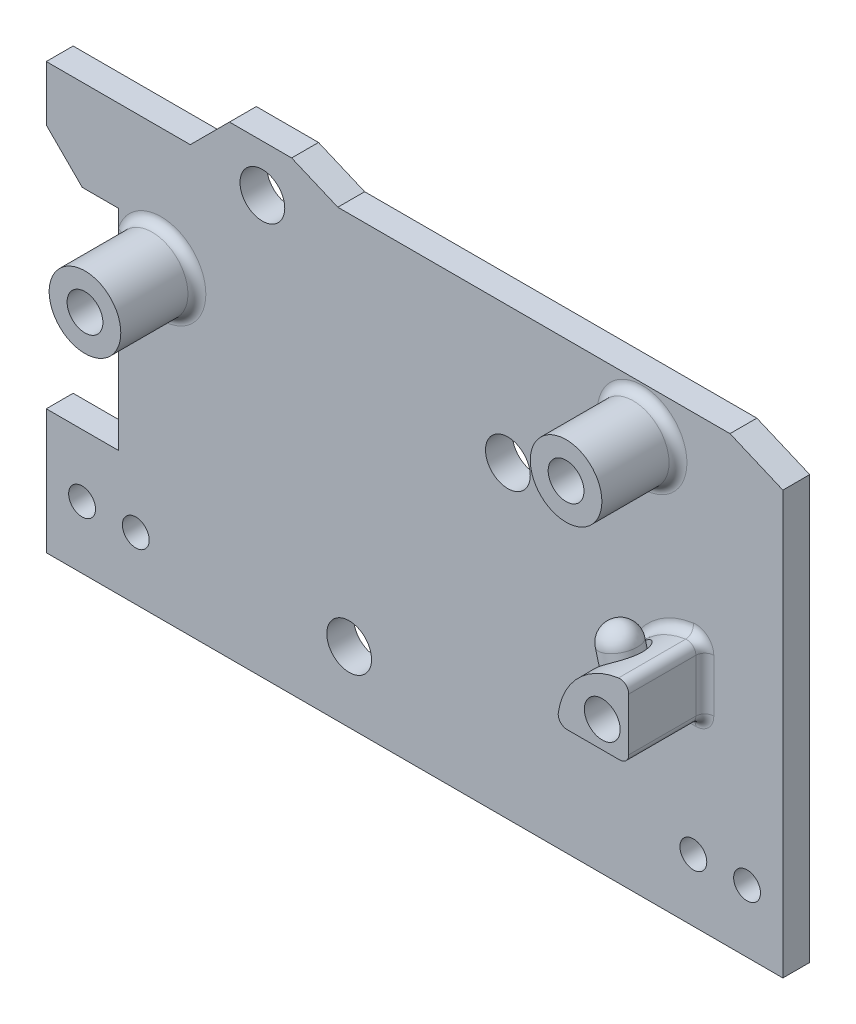
SolidWorks part; units mm, degrees
ref_plane "정면" through (0, 0, 0) normal (0, 0, 1) x (1, 0, 0)
ref_plane "윗면" through (0, 0, 0) normal (0, 1, 0) x (1, 0, 0)
ref_plane "우측면" through (0, 0, 0) normal (1, 0, 0) x (0, 0, -1)
sketch "스케치2" plane through (0, 0, 0) normal (0, 0, 1) x (1, 0, 0)
  line L0 (-41.1383, 21.5701) -> (-25.0531, 21.5701)
  line L1 (-25.0531, 21.5701) -> (-20.6777, 25.9456)
  line L2 (-20.6777, 25.9456) -> (-13.7287, 25.9456)
  line L3 (-13.7287, 25.9456) -> (-8.5741, 23.7579)
  line L4 (-8.5741, 23.7579) -> (35.2319, 23.7579)
  line L5 (35.2319, 23.7579) -> (41.1383, 21.2511)
  line L6 (41.1383, 21.2511) -> (41.1383, -25.9456)
  line L7 (41.1383, -25.9456) -> (-41.1383, -25.9456)
  line L8 (-41.1383, -25.9456) -> (-41.1383, -12.0209)
  line L9 (-41.1383, -12.0209) -> (-33.0957, -12.0209)
  line L10 (-33.0957, -12.0209) -> (-33.0957, 11.4038)
  line L11 (-33.0957, 11.4038) -> (-37.117, 11.4038)
  line L12 (-37.117, 11.4038) -> (-41.1383, 15.4251)
  line L13 (-41.1383, 15.4251) -> (-41.1383, 21.5701)
  line L14 (25.5434, -5.467) -> (31.4219, -5.467)
  line L15 (32.4219, -4.467) -> (32.4219, 1.4115)
  line L16 (32.1291, -5.1741) -> (26.7998, 0.1551) construction
  line L17 (0, 0) -> (-17, 0) construction
  line L18 (-17, 0) -> (-17, 20.7) construction
  circle A0 centre (-17, 20.7) radius 2.5
  circle A1 centre (-28.3144, 7.9767) radius 4
  circle A2 centre (25.4219, 18.533) radius 4
  circle A3 centre (-7.3061, -18.1076) radius 2.5
  circle A4 centre (10.4219, 8.533) radius 2.5
  circle A5 centre (-28.3144, 7.9767) radius 2
  circle A6 centre (25.4219, 18.533) radius 2
  arc A7 (31.2781, 2.4011) -> (24.5538, -4.3232) centre (32.4219, -5.467) ccw
  arc A8 (31.4219, -5.467) -> (32.4219, -4.467) centre (31.4219, -4.467) ccw
  arc A9 (32.4219, 1.4115) -> (31.2781, 2.4011) centre (31.4219, 1.4115) ccw
  arc A10 (25.5434, -5.467) -> (24.5538, -4.3232) centre (25.5434, -4.467) cw
  circle A11 centre (29.4644, -2.5095) radius 2
  point P36 (32.4219, 2.4838)
  point P39 (24.4711, -5.467)
  dimension "D1" = 1
  dimension "D5" = 5
  dimension "D6" = 5
  dimension "D7" = 5
  dimension "D12" = 4
  dimension "D13" = 4
  dimension "D14" = 8
  dimension "D15" = 8
  dimension "D18" = 4
  dimension "D2" = 30
  dimension "D3" = 40
  dimension "D4" = 32
  dimension "D8" = 20.7
  dimension "D9" = 17
  dimension "D10" = 10
  dimension "D11" = 15
  dimension "D16" = 22
  dimension "D17" = 14
  dimension "D19" = 8.0531
extrude "보스-돌출1" add sketch "스케치2" along normal blind 3 contours L13 L12 L11 L10 L9 L8 L7 L6 L5 L4 L3 L2 L1 L0 A4 A3 A2 A1 A0 L14 A10 A7 A9 L15 A8 region at (1.8741, -1.7514, 0)
extrude "보스-돌출2" add sketch "스케치2<3>" along normal blind 11.5 contours A10 L14 A8 L15 A9 A7 A11 | A1 A5 | A2 | A6 region at (24.8714, -5.0484, 0) region at (-32.2013, 7.9767, 0)
sketch "스케치2<3>" plane through (0, 0, 0) normal (0, 0, 1) x (1, 0, 0) same geometry as "스케치2"
sketch "스케치5" plane through (0, 0, 11.5) normal (0, 0, 1) x (1, 0, 0)
  line L0 (32.1291, -5.1741) -> (28.79, 7.2872)
  line L2 (25.5434, -5.467) -> (31.4219, -5.467) construction
  arc A0 (31.4219, -5.467) -> (32.4219, -4.467) centre (31.4219, -4.467) ccw construction
  dimension "D1" = 75
ref_plane "평면1" through (1.4808, -5.5264, 0) normal (-0.2588, 0.9659, 0) x (0, 0, 1)
sketch "스케치6" plane through (1.4808, -5.5264, 0) normal (-0.2588, 0.9659, 0) x (0, 0, 1)
  line L0 (3, 30.8338) -> (11.5, 22.5982) construction
  circle A0 centre (7.25, 26.716) radius 2
extrude "보스-돌출3" add sketch "스케치6" along normal mid plane 4.6 contours A0
fillet "필렛1" radius 2 1 edges at (24.7593, 3.0922, 7.25)
sketch "스케치7" plane through (1.4808, -5.5264, 0) normal (-0.2588, 0.9659, 0) x (0, 0, 1)
  circle A0 centre (7.25, 26.716) radius 2.5
  circle A2 centre (7.25, 26.716) radius 2
extrude "컷-돌출2" cut sketch "스케치7" against normal blind 2
fillet "필렛2" radius 1 8 edges at (32.0762, 2.1678, 3) (32.4219, -1.5278, 3) (32.1291, -5.1741, 3) (28.4827, -5.467, 3) (24.7871, -5.1213, 3) (-24.3144, 7.9767, 3) (29.4219, 18.533, 3) (26.7998, 0.1551, 3)
sketch "스케치8" plane through (0, 0, 3) normal (0, 0, 1) x (1, 0, 0)
  line L0 (41.1383, -25.9456) -> (-41.1383, -25.9456) construction
  line L4 (-41.1383, -25.9456) -> (-41.1383, -12.0209) construction
  circle A0 centre (-37.1383, -18.9833) radius 1.5
  circle A1 centre (-31.1383, -18.9833) radius 1.5
  point P10 (-41.1383, -18.9833)
  dimension "D2" = 3
  dimension "D4" = 3
  dimension "D1" = 6.9624
  dimension "D3" = 4
  dimension "D5" = 6
  dimension "D6" = 6.9624
sketch "스케치9" plane through (0, 0, 3) normal (0, 0, 1) x (1, 0, 0)
extrude "컷-돌출3" cut sketch "스케치8" against normal up to next
sketch "스케치10" plane through (0, 0, 3) normal (0, 0, 1) x (1, 0, 0)
sketch "스케치11" plane through (0, 0, 3) normal (0, 0, 1) x (1, 0, 0)
  line L0 (41.1383, 21.2511) -> (41.1383, -25.9456) construction
  line L2 (41.1383, -25.9456) -> (-41.1383, -25.9456) construction
  circle A0 centre (37.1383, -18.9833) radius 1.5
  circle A1 centre (31.1383, -18.9833) radius 1.5
  point P3 (38.0102, -19.6876)
  point P4 (23.5872, -18.0006)
  point P9 (27.2362, -19.6014)
  dimension "D2" = 3
  dimension "D3" = 3
  dimension "D1" = 6.9624
  dimension "D4" = 6
  dimension "D5" = 6.9624
  dimension "D6" = 4
extrude "컷-돌출4" cut sketch "스케치11" against normal up to next
